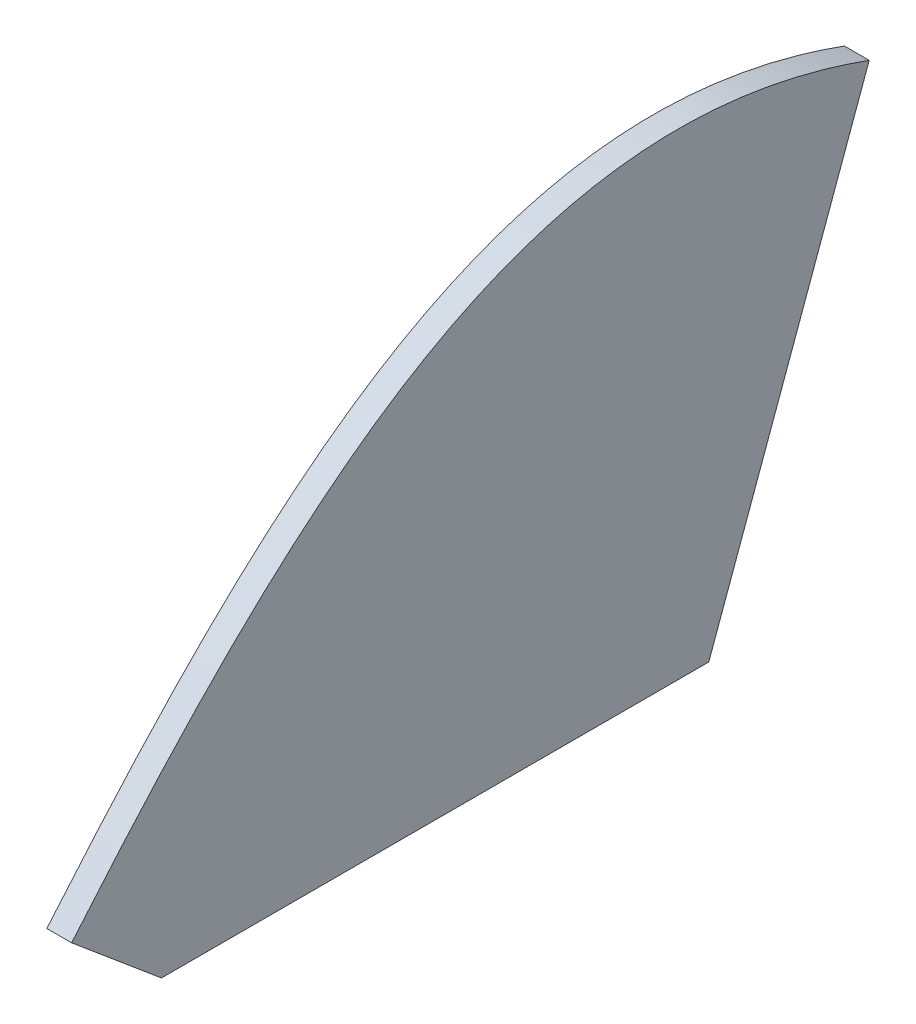
SolidWorks part; units mm, degrees
ref_plane "Front Plane" through (0, 0, 0) normal (0, 0, 1) x (1, 0, 0)
ref_plane "Top Plane" through (0, 0, 0) normal (0, 1, 0) x (1, 0, 0)
ref_plane "Right Plane" through (0, 0, 0) normal (1, 0, 0) x (0, 0, -1)
sketch "Sketch1" plane through (0, 0, 0) normal (1, 0, 0) x (0, 0, -1)
  line L0 (0, 0) -> (70, 0)
  line L1 (70, 0) -> (90.5212, 56.3816)
  line L2 (0, 0) -> (-11.4907, 9.6418)
  line L3 (132.6983, 41.0304) -> (48.3441, 71.7328) construction
  line L4 (16.7294, 43.2732) -> (-39.7107, -23.9895) construction
  spline S0 degree 3 poles (-11.4907, 9.6418) (19.4561, 46.5227) (48.0161, 71.8522) (90.5212, 56.3816) knots 0 0 0 0 1 1 1 1
  dimension "D1" = 70
  dimension "D2" = 110
  dimension "D3" = 60
  dimension "D4" = 140
  dimension "D5" = 15
extrude "Boss-Extrude1" add sketch "Sketch1" along normal blind 3.175 contours L2 S0 L1 L0
